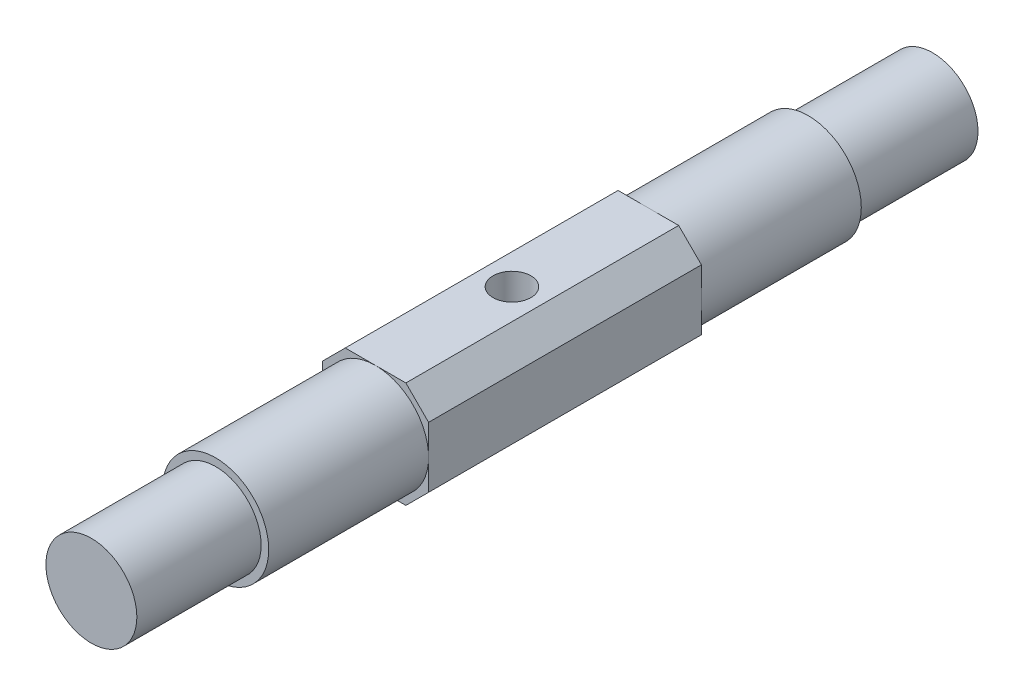
SolidWorks part; units mm, degrees
ref_plane "Alzado" through (0, 0, 0) normal (0, 0, 1) x (1, 0, 0)
ref_plane "Planta" through (0, 0, 0) normal (0, 1, 0) x (1, 0, 0)
ref_plane "Vista lateral" through (0, 0, 0) normal (1, 0, 0) x (0, 0, -1)
sketch "Croquis1" plane through (0, 0, 0) normal (0, 0, 1) x (1, 0, 0)
  circle A0 centre (0, 0) radius 3
extrude "Saliente-Extruir1" add sketch "Croquis1" along normal blind 8.2
sketch "Croquis2" plane through (0, 0, 8.2) normal (0, 0, 1) x (1, 0, 0)
  circle A0 centre (0, 0) radius 3.5
extrude "Saliente-Extruir2" add sketch "Croquis2" along normal blind 10.55
sketch "Croquis3" plane through (0, 0, 18.75) normal (0, 0, 1) x (1, 0, 0)
  line L1 (3.5, -3.5) -> (-3.5, -3.5)
  line L2 (3.5, -3.5) -> (3.5, 3.5)
  line L3 (3.5, 3.5) -> (-3.5, 3.5)
  line L4 (-3.5, -3.5) -> (-3.5, 3.5)
  line L5 (3.5, -3.5) -> (-3.5, 3.5) construction
  line L6 (3.5, 3.5) -> (-3.5, -3.5) construction
  point P0 (0, 0)
  dimension "D1" = 7
  dimension "D2" = 7
extrude "Saliente-Extruir3" add sketch "Croquis3" along normal blind 18 contours L3 L4 L1 L2
sketch "Croquis4" plane through (0, 0, 36.75) normal (0, 0, 1) x (1, 0, 0)
  circle A0 centre (0, 0) radius 3.5
extrude "Saliente-Extruir4" add sketch "Croquis4" along normal blind 10.55
sketch "Croquis5" plane through (0, 0, 47.3) normal (0, 0, 1) x (1, 0, 0)
  circle A0 centre (0, 0) radius 3
extrude "Saliente-Extruir5" add sketch "Croquis5" along normal blind 8.2
sketch "Croquis6" plane through (0, 3.5, 0) normal (0, 1, 0) x (1, 0, 0)
  circle A0 centre (0, -27.75) radius 1.25
  dimension "D1" = 9
extrude "Cortar-Extruir1" cut sketch "Croquis6" against normal through all
chamfer "Chaflán1" distance 1.5 angle 45 4 edges at (3.5, -3.5, 27.75) (3.5, 3.5, 27.75) (-3.5, -3.5, 27.75) (-3.5, 3.5, 27.75)
